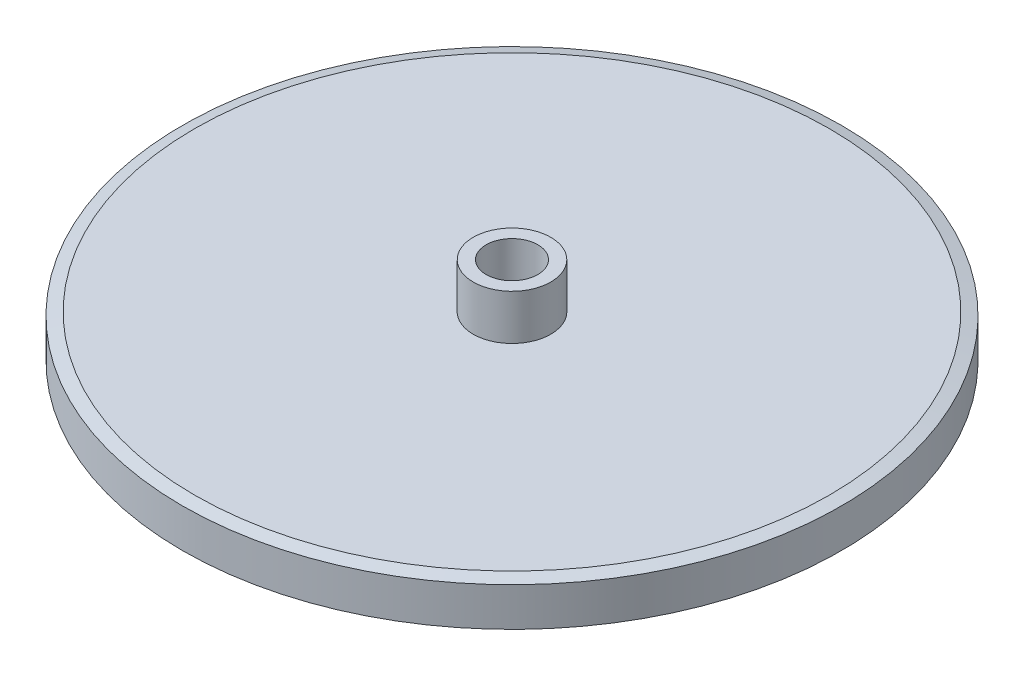
SolidWorks part; units mm, degrees
material "Сталь ШХ15 ГОСТ 801-78"
ref_plane "Plane1" through (0, 0, 0) normal (0, 0, 1) x (1, 0, 0)
ref_plane "Plane2" through (0, 0, 0) normal (0, 1, 0) x (1, 0, 0)
ref_plane "Plane3" through (0, 0, 0) normal (1, 0, 0) x (0, 0, -1)
sketch "Эскиз1" plane through (0, 0, 0) normal (0, 0, 1) x (1, 0, 0)
  line L0 (0, 0) -> (25.5, 0)
  line L1 (25.5, 0) -> (25.5, 3.5)
  line L2 (25.5, 3.5) -> (3, 3.5)
  line L3 (3, 3.5) -> (3, 7)
  line L4 (3, 7) -> (0, 7)
  line L5 (0, 7) -> (0, 0)
  dimension "D1" = 3.5
  dimension "30" = 25.5
  dimension "D3" = 3
  dimension "D4" = 3.5
ref_axis "Ось1" through (0, 7, 0) along (0, -1, 0)
revolve "Повернуть2" add sketch "Эскиз1" angle 360 about axis through (0, 7, 0) along (0, -1, 0)
chamfer "Фаска1" distance 0.94 angle 15 1 edges at (0, 3.5, 25.5) first distance on face at (0, 3.5, 3)
sketch "Эскиз2" plane through (0, 0, 0) normal (0, -1, 0) x (-1, 0, 0)
  circle A0 centre (0, 0) radius 2
  dimension "D1" = 4
sketch "Эскиз3" plane through (0, 0, 0) normal (1, 0, 0) x (0, 0, -1)
  circle A0 centre (0, 7.4791) radius 1
extrude "Вырез-Вытянуть3" cut sketch "Эскиз2" against normal through all both
chamfer "Фаска2" distance 0.94 angle 15 1 edges at (0, 0, 25.5) first distance on face at (0, 0, -2)
